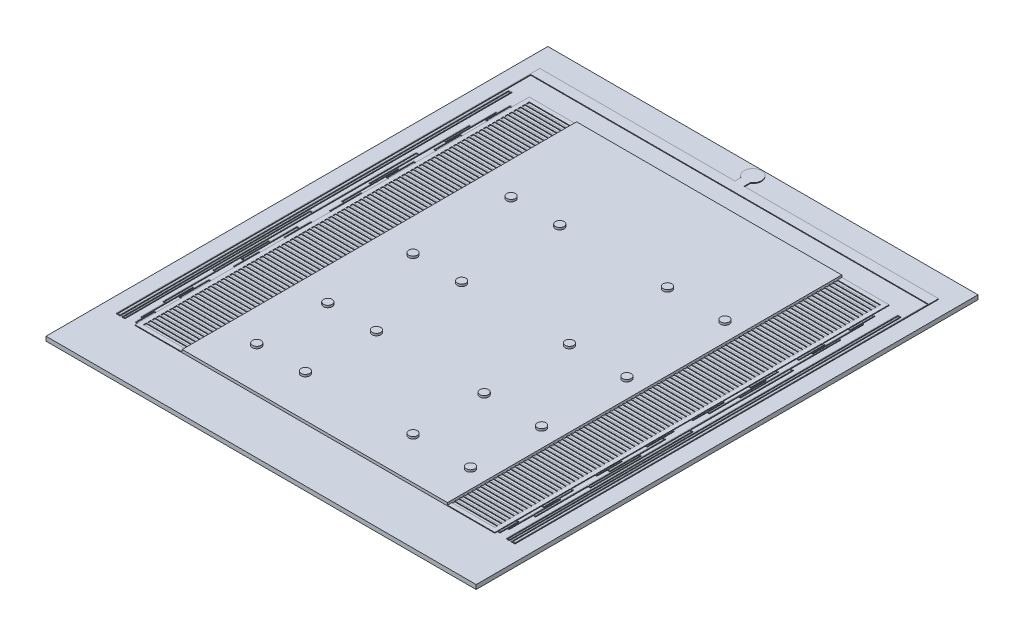
SolidWorks part; units mm, degrees
ref_plane "Front Plane" through (0, 0, 0) normal (0, 0, 1) x (1, 0, 0)
ref_plane "Top Plane" through (0, 0, 0) normal (0, 1, 0) x (1, 0, 0)
ref_plane "Right Plane" through (0, 0, 0) normal (1, 0, 0) x (0, 0, -1)
sketch "Sketch3" plane through (0, 0, 0) normal (0, 1, 0) x (1, 0, 0)
  line L1 (-15, 17.5) -> (15, 17.5)
  line L2 (-15, 17.5) -> (-15, -17.5)
  line L3 (-15, -17.5) -> (15, -17.5)
  line L4 (15, 17.5) -> (15, -17.5)
  line L5 (-15, 17.5) -> (15, -17.5) construction
  line L6 (-15, -17.5) -> (15, 17.5) construction
  point P0 (0, 0)
  dimension "D1" = 30
  dimension "D2" = 35
extrude "Boss-Extrude2" add sketch "Sketch3" along normal blind 0.3
sketch "Sketch4" plane through (0, 0.3, 0) normal (0, 1, 0) x (1, 0, 0)
  line L1 (-9.25, 13.75) -> (9.25, 13.75)
  line L2 (-9.25, 13.75) -> (-9.25, -13.75)
  line L3 (-9.25, -13.75) -> (9.25, -13.75)
  line L4 (9.25, 13.75) -> (9.25, -13.75)
  line L5 (-9.25, 13.75) -> (9.25, -13.75) construction
  line L6 (-9.25, -13.75) -> (9.25, 13.75) construction
  point P0 (0, 0)
  dimension "D1" = 18.5
  dimension "D2" = 27.5
sketch "Sketch6" plane through (0, 0.3, 0) normal (0, 1, 0) x (1, 0, 0)
  line L0 (-13.905, 15.8474) -> (13.905, 15.8474)
  line L1 (13.905, 15.8474) -> (13.905, -13.6942)
  line L2 (-13.905, 15.8474) -> (-13.905, -13.6942)
  line L3 (-9.25, 13.75) -> (-9.25, -13.75)
  line L4 (-9.25, 13.75) -> (-12.55, 13.75)
  line L5 (-9.25, -13.75) -> (-12.55, -13.75)
  line L6 (-12.55, 13.75) -> (-12.55, -13.75)
  line L7 (9.25, 13.75) -> (9.25, -13.75)
  line L8 (9.25, 13.75) -> (12.55, 13.75)
  line L9 (9.25, -13.75) -> (12.55, -13.75)
  line L10 (12.55, 13.75) -> (12.55, -13.75)
  line L11 (-12.55, 12.5818) -> (-12.7178, 12.5818)
  line L12 (-12.55, 12.5318) -> (-12.6678, 12.5318)
  line L13 (-12.55, 10.928) -> (-12.6678, 10.928)
  line L14 (-12.55, 10.878) -> (-12.7178, 10.878)
  line L15 (-12.6678, 12.5318) -> (-12.6678, 10.928)
  line L16 (-12.7178, 12.5818) -> (-12.7178, 11.7021)
  line L17 (-12.7178, 11.7021) -> (-12.8193, 11.7021)
  line L18 (-12.7178, 10.878) -> (-12.7178, 11.6521)
  line L19 (-12.7178, 11.6521) -> (-12.7693, 11.6521)
  line L20 (-12.55, 9.1125) -> (-12.7178, 9.1125)
  line L21 (-12.55, 9.0625) -> (-12.6678, 9.0625)
  line L22 (-12.6678, 9.0625) -> (-12.6678, 7.3412)
  line L23 (-12.6678, 7.3412) -> (-12.55, 7.3412)
  line L24 (-12.55, 7.2912) -> (-12.7178, 7.2912)
  line L25 (-12.7178, 7.2912) -> (-12.7178, 8.1575)
  line L26 (-12.8193, 11.7021) -> (-12.8193, 9.9736)
  line L27 (-12.7178, 9.1125) -> (-12.7178, 8.2075)
  line L28 (-12.7178, 8.2075) -> (-12.7693, 8.2075)
  line L29 (-12.55, 5.8632) -> (-12.7178, 5.8632)
  line L30 (-12.7178, 5.8632) -> (-12.7178, 4.8722)
  line L31 (-12.7178, 4.8722) -> (-12.8274, 4.8722)
  line L32 (-12.55, 3.9456) -> (-12.7178, 3.9456)
  line L33 (-12.7178, 3.9456) -> (-12.7178, 4.8222)
  line L34 (-12.7178, 4.8222) -> (-12.7774, 4.8222)
  line L35 (-12.55, 5.8132) -> (-12.6678, 5.8132)
  line L36 (-12.6678, 5.8132) -> (-12.6678, 3.9956)
  line L37 (-12.6678, 3.9956) -> (-12.55, 3.9956)
  line L38 (-12.55, 2.1314) -> (-12.6674, 2.1314)
  line L39 (-12.6674, 2.1314) -> (-12.6674, 0.9895)
  line L40 (-12.6674, 0.9895) -> (-12.7774, 0.9895)
  line L41 (-12.55, -0.05) -> (-12.6674, -0.05)
  line L42 (-12.6674, -0.05) -> (-12.6674, 0.9395)
  line L43 (-12.8274, 4.8722) -> (-12.8274, 3.0344)
  line L44 (-12.55, 2.0814) -> (-12.6174, 2.0814)
  line L45 (-12.6174, 2.0814) -> (-12.6174, 0)
  line L46 (-12.6174, 0) -> (-12.55, 0)
  line L47 (-12.55, -1.363) -> (-12.6674, -1.363)
  line L48 (-12.6674, -1.363) -> (-12.6674, -2.1377)
  line L49 (-12.8274, 3.0344) -> (-12.9034, 3.0344)
  line L50 (-12.55, -3.2374) -> (-12.6674, -3.2374)
  line L51 (-12.6674, -3.2374) -> (-12.6674, -2.1877)
  line L52 (-12.6674, -2.1877) -> (-12.8051, -2.1877)
  line L53 (-12.55, -1.413) -> (-12.6174, -1.413)
  line L54 (-12.6174, -1.413) -> (-12.6174, -3.1874)
  line L55 (-12.6174, -3.1874) -> (-12.55, -3.1874)
  line L56 (-12.55, -4.9884) -> (-12.6674, -4.9884)
  line L57 (-12.6674, -4.9884) -> (-12.6674, -5.9807)
  line L58 (-12.6674, -5.9807) -> (-12.8051, -5.9807)
  line L59 (-12.55, -6.7484) -> (-12.6674, -6.7484)
  line L60 (-12.6674, -6.7484) -> (-12.6674, -6.0307)
  line L61 (-12.6674, 0.9395) -> (-12.8274, 0.9395)
  line L62 (-12.6174, -5.0384) -> (-12.6174, -6.6984)
  line L63 (-12.6174, -6.6984) -> (-12.55, -6.6984)
  line L64 (-12.6174, -5.0384) -> (-12.55, -5.0384)
  line L65 (-12.55, -8.422) -> (-12.7178, -8.422)
  line L66 (-12.7178, -8.422) -> (-12.7178, -9.4377)
  line L67 (-12.8274, 0.9395) -> (-12.8274, 2.9844)
  line L68 (-12.55, -10.502) -> (-12.7178, -10.502)
  line L69 (-12.7178, -10.502) -> (-12.7178, -9.4877)
  line L70 (-12.7178, -9.4877) -> (-12.7793, -9.4877)
  line L71 (-12.55, -8.472) -> (-12.6678, -8.472)
  line L72 (-12.6678, -8.472) -> (-12.6678, -10.452)
  line L73 (-12.6678, -10.452) -> (-12.55, -10.452)
  line L74 (-12.55, -12.2327) -> (-12.7178, -12.2327)
  line L75 (-12.7178, -12.2327) -> (-12.7178, -12.9898)
  line L76 (-12.7178, -12.9898) -> (-12.7793, -12.9898)
  line L77 (-12.55, -13.5571) -> (-12.7178, -13.5571)
  line L78 (-12.7178, -13.5571) -> (-12.7178, -13.0398)
  line L79 (-12.8193, 9.9736) -> (-12.9534, 9.9736)
  line L80 (-12.6678, -12.2827) -> (-12.6678, -13.5071)
  line L81 (-12.6678, -13.5071) -> (-12.55, -13.5071)
  line L82 (-12.9534, 9.9736) -> (-12.9534, 6.4717)
  line L83 (-12.7178, 8.1575) -> (-12.8193, 8.1575)
  line L84 (-12.8193, 8.1575) -> (-12.8193, 9.9236)
  line L85 (-12.8193, 9.9236) -> (-12.9034, 9.9236)
  line L86 (-12.7693, 11.6521) -> (-12.7693, 8.2075)
  line L87 (-12.7774, 4.8222) -> (-12.7774, 0.9895)
  line L88 (-12.6674, -6.0307) -> (-12.8551, -6.0307)
  line L89 (-12.8551, -6.0307) -> (-12.8551, -4.0382)
  line L90 (-12.8551, -4.0382) -> (-12.9467, -4.0382)
  line L91 (-12.6674, -2.1377) -> (-12.8551, -2.1377)
  line L92 (-12.8551, -2.1377) -> (-12.8551, -3.9882)
  line L93 (-12.8551, -3.9882) -> (-12.9967, -3.9882)
  line L94 (-12.8051, -2.1877) -> (-12.8051, -5.9807)
  line L95 (-12.7178, -9.4377) -> (-12.8293, -9.4377)
  line L96 (-12.8293, -9.4377) -> (-12.8293, -11.3027)
  line L97 (-12.8293, -11.3027) -> (-12.9467, -11.3027)
  line L98 (-12.7178, -13.0398) -> (-12.8293, -13.0398)
  line L99 (-12.8293, -13.0398) -> (-12.8293, -11.3527)
  line L100 (-12.9967, -3.9882) -> (-12.9967, -7.6362)
  line L101 (-12.7793, -9.4877) -> (-12.7793, -12.9898)
  line L102 (-12.9534, 6.4717) -> (-13.1543, 6.4717)
  line L103 (-12.9534, 2.9844) -> (-12.9534, 6.4217)
  line L104 (-12.9534, 6.4217) -> (-13.1043, 6.4217)
  line L105 (-12.9034, 9.9236) -> (-12.9034, 3.0344)
  line L106 (-12.9534, 2.9844) -> (-12.8274, 2.9844)
  line L107 (-12.9967, -7.6362) -> (-13.1043, -7.6362)
  line L108 (-12.8293, -11.3527) -> (-12.9967, -11.3527)
  line L109 (-12.9967, -11.3527) -> (-12.9967, -7.6862)
  line L110 (-13.1543, 6.4717) -> (-13.1543, -0.7267)
  line L111 (-12.9467, -4.0382) -> (-12.9467, -11.3027)
  line L112 (-13.1543, -0.7267) -> (-13.3496, -0.7267)
  line L113 (-12.9967, -7.6862) -> (-13.1543, -7.6862)
  line L114 (-13.1543, -7.6862) -> (-13.1543, -0.7767)
  line L115 (-13.1043, -7.6362) -> (-13.1043, 6.4217)
  line L116 (-12.6678, -12.2827) -> (-12.55, -12.2827)
  line L117 (-13.905, -13.6942) -> (-13.6359, -13.6942)
  line L118 (-13.855, 15.1627) -> (13.855, 15.1627)
  line L119 (-13.855, 15.1627) -> (-13.855, -13.6442)
  line L120 (-13.855, -13.6442) -> (-13.6859, -13.6442)
  line L121 (-13.6859, -13.6442) -> (-13.6859, 13.4436)
  line L122 (-13.6859, 13.4436) -> (-13.461, 13.4436)
  line L123 (-13.461, 13.4436) -> (-13.461, -13.646)
  line L124 (-13.461, -13.646) -> (-13.3496, -13.646)
  line L125 (-13.3496, -13.646) -> (-13.3496, -0.7267)
  line L126 (-13.6359, -13.6942) -> (-13.6359, 13.3936)
  line L127 (-13.6359, 13.3936) -> (-13.511, 13.3936)
  line L128 (-13.511, 13.3936) -> (-13.511, -13.696)
  line L129 (-13.511, -13.696) -> (-13.2996, -13.696)
  line L130 (-13.2996, -13.696) -> (-13.2996, -0.7767)
  line L131 (-13.2996, -0.7767) -> (-13.1543, -0.7767)
  line L132 (0, -18.8163) -> (0, 18.8163) construction
  line L134 (13.855, 15.1627) -> (13.855, -13.6442)
  line L135 (13.511, -13.696) -> (13.2996, -13.696)
  line L136 (13.461, -13.646) -> (13.3496, -13.646)
  line L137 (13.905, -13.6942) -> (13.6359, -13.6942)
  line L138 (13.855, -13.6442) -> (13.6859, -13.6442)
  line L139 (12.7178, -13.5571) -> (12.7178, -13.0398)
  line L140 (12.55, -13.5571) -> (12.7178, -13.5571)
  line L141 (12.6678, -13.5071) -> (12.55, -13.5071)
  line L142 (12.7178, -13.0398) -> (12.8293, -13.0398)
  line L143 (12.7178, -12.9898) -> (12.7793, -12.9898)
  line L144 (12.6678, -12.2827) -> (12.55, -12.2827)
  line L145 (12.7178, -12.2327) -> (12.7178, -12.9898)
  line L146 (12.6678, -12.2827) -> (12.6678, -13.5071)
  line L147 (12.55, -12.2327) -> (12.7178, -12.2327)
  line L148 (12.8293, -13.0398) -> (12.8293, -11.3527)
  line L149 (12.8293, -11.3527) -> (12.9967, -11.3527)
  line L150 (12.8293, -11.3027) -> (12.9467, -11.3027)
  line L151 (12.55, -10.502) -> (12.7178, -10.502)
  line L152 (12.6678, -10.452) -> (12.55, -10.452)
  line L153 (12.7178, -10.502) -> (12.7178, -9.4877)
  line L154 (12.8293, -9.4377) -> (12.8293, -11.3027)
  line L155 (12.7793, -9.4877) -> (12.7793, -12.9898)
  line L156 (12.7178, -9.4877) -> (12.7793, -9.4877)
  line L157 (12.7178, -9.4377) -> (12.8293, -9.4377)
  line L158 (12.7178, -8.422) -> (12.7178, -9.4377)
  line L159 (12.6678, -8.472) -> (12.6678, -10.452)
  line L160 (12.55, -8.472) -> (12.6678, -8.472)
  line L161 (12.55, -8.422) -> (12.7178, -8.422)
  line L162 (12.9967, -11.3527) -> (12.9967, -7.6862)
  line L163 (12.9967, -7.6862) -> (13.1543, -7.6862)
  line L164 (12.9967, -7.6362) -> (13.1043, -7.6362)
  line L165 (12.55, -6.7484) -> (12.6674, -6.7484)
  line L166 (12.6174, -6.6984) -> (12.55, -6.6984)
  line L167 (12.6674, -6.7484) -> (12.6674, -6.0307)
  line L168 (12.6674, -6.0307) -> (12.8551, -6.0307)
  line L169 (12.6674, -5.9807) -> (12.8051, -5.9807)
  line L170 (12.6674, -4.9884) -> (12.6674, -5.9807)
  line L171 (12.6174, -5.0384) -> (12.6174, -6.6984)
  line L172 (12.6174, -5.0384) -> (12.55, -5.0384)
  line L173 (12.55, -4.9884) -> (12.6674, -4.9884)
  line L174 (12.8551, -6.0307) -> (12.8551, -4.0382)
  line L175 (12.9967, -3.9882) -> (12.9967, -7.6362)
  line L176 (12.9467, -4.0382) -> (12.9467, -11.3027)
  line L177 (12.8551, -4.0382) -> (12.9467, -4.0382)
  line L178 (12.8551, -3.9882) -> (12.9967, -3.9882)
  line L179 (12.55, -3.2374) -> (12.6674, -3.2374)
  line L180 (12.6174, -3.1874) -> (12.55, -3.1874)
  line L181 (12.8551, -2.1377) -> (12.8551, -3.9882)
  line L182 (12.8051, -2.1877) -> (12.8051, -5.9807)
  line L183 (12.6674, -3.2374) -> (12.6674, -2.1877)
  line L184 (12.6674, -2.1877) -> (12.8051, -2.1877)
  line L185 (12.6674, -2.1377) -> (12.8551, -2.1377)
  line L186 (12.6174, -1.413) -> (12.6174, -3.1874)
  line L187 (12.6674, -1.363) -> (12.6674, -2.1377)
  line L188 (12.55, -1.413) -> (12.6174, -1.413)
  line L189 (12.55, -1.363) -> (12.6674, -1.363)
  line L190 (13.1543, -7.6862) -> (13.1543, -0.7767)
  line L191 (13.2996, -13.696) -> (13.2996, -0.7767)
  line L192 (13.3496, -13.646) -> (13.3496, -0.7267)
  line L193 (13.2996, -0.7767) -> (13.1543, -0.7767)
  line L194 (13.1543, -0.7267) -> (13.3496, -0.7267)
  line L195 (12.55, -0.05) -> (12.6674, -0.05)
  line L196 (12.6174, 0) -> (12.55, 0)
  line L197 (12.6674, -0.05) -> (12.6674, 0.9395)
  line L198 (12.6674, 0.9395) -> (12.8274, 0.9395)
  line L199 (12.6674, 0.9895) -> (12.7774, 0.9895)
  line L200 (12.6174, 2.0814) -> (12.6174, 0)
  line L201 (12.6674, 2.1314) -> (12.6674, 0.9895)
  line L202 (12.55, 2.0814) -> (12.6174, 2.0814)
  line L203 (12.55, 2.1314) -> (12.6674, 2.1314)
  line L204 (12.8274, 3.0344) -> (12.9034, 3.0344)
  line L205 (12.9534, 2.9844) -> (12.8274, 2.9844)
  line L206 (12.8274, 0.9395) -> (12.8274, 2.9844)
  line L207 (12.55, 3.9456) -> (12.7178, 3.9456)
  line L208 (12.6678, 3.9956) -> (12.55, 3.9956)
  line L209 (12.8274, 4.8722) -> (12.8274, 3.0344)
  line L210 (12.7774, 4.8222) -> (12.7774, 0.9895)
  line L211 (12.7178, 3.9456) -> (12.7178, 4.8222)
  line L212 (12.7178, 4.8222) -> (12.7774, 4.8222)
  line L213 (12.7178, 4.8722) -> (12.8274, 4.8722)
  line L214 (12.6678, 5.8132) -> (12.6678, 3.9956)
  line L215 (12.7178, 5.8632) -> (12.7178, 4.8722)
  line L216 (12.55, 5.8132) -> (12.6678, 5.8132)
  line L217 (12.55, 5.8632) -> (12.7178, 5.8632)
  line L218 (12.9534, 2.9844) -> (12.9534, 6.4217)
  line L219 (13.1543, 6.4717) -> (13.1543, -0.7267)
  line L220 (13.1043, -7.6362) -> (13.1043, 6.4217)
  line L221 (12.9534, 6.4217) -> (13.1043, 6.4217)
  line L222 (12.9534, 6.4717) -> (13.1543, 6.4717)
  line L223 (12.55, 7.2912) -> (12.7178, 7.2912)
  line L224 (12.6678, 7.3412) -> (12.55, 7.3412)
  line L225 (12.7178, 7.2912) -> (12.7178, 8.1575)
  line L226 (12.7178, 8.1575) -> (12.8193, 8.1575)
  line L227 (12.7178, 8.2075) -> (12.7693, 8.2075)
  line L228 (12.6678, 9.0625) -> (12.6678, 7.3412)
  line L229 (12.7178, 9.1125) -> (12.7178, 8.2075)
  line L230 (12.55, 9.0625) -> (12.6678, 9.0625)
  line L231 (12.55, 9.1125) -> (12.7178, 9.1125)
  line L232 (12.8193, 8.1575) -> (12.8193, 9.9236)
  line L233 (12.9534, 9.9736) -> (12.9534, 6.4717)
  line L234 (12.9034, 9.9236) -> (12.9034, 3.0344)
  line L235 (12.8193, 9.9236) -> (12.9034, 9.9236)
  line L236 (12.8193, 9.9736) -> (12.9534, 9.9736)
  line L237 (12.55, 10.878) -> (12.7178, 10.878)
  line L238 (12.55, 10.928) -> (12.6678, 10.928)
  line L239 (12.8193, 11.7021) -> (12.8193, 9.9736)
  line L240 (12.7693, 11.6521) -> (12.7693, 8.2075)
  line L241 (12.7178, 10.878) -> (12.7178, 11.6521)
  line L242 (12.7178, 11.6521) -> (12.7693, 11.6521)
  line L243 (12.7178, 11.7021) -> (12.8193, 11.7021)
  line L244 (13.461, 13.4436) -> (13.461, -13.646)
  line L245 (13.511, 13.3936) -> (13.511, -13.696)
  line L246 (13.6359, -13.6942) -> (13.6359, 13.3936)
  line L247 (13.6859, -13.6442) -> (13.6859, 13.4436)
  line L248 (13.6359, 13.3936) -> (13.511, 13.3936)
  line L249 (13.6859, 13.4436) -> (13.461, 13.4436)
  line L250 (12.6678, 12.5318) -> (12.6678, 10.928)
  line L251 (12.7178, 12.5818) -> (12.7178, 11.7021)
  line L252 (12.55, 12.5318) -> (12.6678, 12.5318)
  line L253 (12.55, 12.5818) -> (12.7178, 12.5818)
  line L254 (-0.2968, 16.2659) -> (-0.2968, 15.8474)
  line L255 (0.336, 16.2899) -> (0.336, 15.8474)
  circle A0 centre (0, 16.7949) radius 0.6065
  point P0 (-12.55, 0)
  point P3 (0, 15.8474)
  point P14 (-12.55, 0)
  point P19 (-12.55, 7.2912)
  point P21 (-12.55, 10.928)
  point P22 (-12.55, 12.4686)
  point P23 (-12.55, 9.0625)
  point P24 (-12.55, 3.9833)
  point P25 (-12.55, 5.8132)
  point P26 (-12.55, 2.0814)
  point P27 (-12.55, -6.7484)
  point P28 (-12.55, -3.2374)
  point P29 (-12.55, -1.413)
  point P30 (-12.55, -5.0384)
  point P31 (-12.55, -10.502)
  point P32 (-12.55, -8.472)
  point P33 (-12.55, -12.1448)
  point P157 (-13.227, -0.7767)
  point P158 (-12.5837, -6.6984)
  point P162 (0, 15.1627)
  point P177 (0, 0)
  dimension "D1" = 3.3
  dimension "D2" = 3.3
  dimension "D3" = 27.81
  dimension "D4" = 0.05
  dimension "D5" = 0.05
  dimension "D6" = 0.05
  dimension "D7" = 0.05
  dimension "D8" = 0.05
  dimension "D9" = 0.05
  dimension "D10" = 0.05
  dimension "D11" = 0.05
  dimension "D12" = 0.05
  dimension "D13" = 0.05
  dimension "D14" = 0.05
  dimension "D15" = 0.05
  dimension "D16" = 0.05
  dimension "D17" = 0.05
  dimension "D18" = 0.05
  dimension "D19" = 0.05
  dimension "D20" = 0.05
  dimension "D21" = 0.05
  dimension "D22" = 0.05
  dimension "D23" = 0.05
  dimension "D24" = 0.05
  dimension "D25" = 0.05
  dimension "D26" = 0.05
  dimension "D27" = 0.05
  dimension "D28" = 0.05
  dimension "D29" = 0.05
  dimension "D30" = 0.05
  dimension "D31" = 0.05
  dimension "D32" = 0.05
  dimension "D33" = 0.05
  dimension "D34" = 0.05
  dimension "D35" = 0.05
  dimension "D36" = 0.05
  dimension "D37" = 0.05
  dimension "D38" = 0.05
  dimension "D39" = 0.05
  dimension "D40" = 0.05
  dimension "D41" = 0.05
  dimension "D42" = 0.05
  dimension "D43" = 0.05
  dimension "D44" = 0.05
  dimension "D45" = 0.05
  dimension "D46" = 0.05
  dimension "D47" = 0.05
  dimension "D48" = 0.05
  dimension "D49" = 0.05
  dimension "D50" = 0.05
  dimension "D51" = 0.05
  dimension "D52" = 0.05
  dimension "D53" = 0.05
  dimension "D54" = 0.05
  dimension "D55" = 0.05
  dimension "D56" = 0.05
extrude "Boss-Extrude5" add sketch "Sketch4" along normal blind 0.2 separate body
extrude "Boss-Extrude10" add sketch "Sketch6" along normal blind 0.05 contours L132 L118 L134 L138 L247 L249 L244 L136 L192 L194 L219 L222 L233 L236 L239 L243 L251 L253 L10 L252 L250 L238 L237 L241 L242 L240 L227 L229 L231 L230 L228 L224 L223 L225 L226 L232 L235 L234 L204 L209 L213 L215 L217 L216 L214 L208 | L0 L132 A0 L254 | L132 L0 L255 A0 | A0 L132 | L132 A0 | L118 L132 L0 L2 L117 L126 L127 L128 L129 L130 L131 L114 L113 L109 L108 L99 L98 L78 L77 L6 L81 L80 L116 L74 L75 L76 L101 L70 L69 L68 L73 L72 L71 L65 L66 L95 L96 L97 L111 L90 L89 L88 L60 L59 L63 L62 | L10 L8 L7 L9 | L4 L6 L5 L3 | L3 L4 L6 L5 | L7 L8 L10 L9 region at (-7.1009, 0.3, -15.5209) region at (-0.1536, 0.3, -16.0312) region at (0.1754, 0.3, -16.0354) region at (0.168, 0.3, -15.5209) region at (-0.2574, 0.3, -16.7949) region at (0.2574, 0.3, -16.7949) region at (-10.9, 0.3, 0) region at (10.9, 0.3, 0)
sketch "Sketch7" plane through (0, 0.3, 0) normal (0, 1, 0) x (1, 0, 0)
  line L0 (9.25, 13.45) -> (12.25, 13.45)
  line L1 (9.25, 13.45) -> (9.25, 13.25)
  line L2 (12.25, 13.45) -> (12.25, 13.25)
  line L3 (9.25, 13.25) -> (12.25, 13.25)
  line L4 (9.25, -13.75) -> (9.25, 13.75) construction
  line L7 (9.25, 13.15) -> (12.25, 13.15)
  line L8 (9.25, 13.15) -> (9.25, 12.95)
  line L9 (9.25, 12.95) -> (12.25, 12.95)
  line L10 (12.25, 13.15) -> (12.25, 12.95)
  line L11 (9.25, 12.85) -> (12.25, 12.85)
  line L12 (9.25, 12.85) -> (9.25, 12.65)
  line L13 (9.25, 12.65) -> (12.25, 12.65)
  line L14 (12.25, 12.85) -> (12.25, 12.65)
  line L15 (9.25, 12.55) -> (12.25, 12.55)
  line L16 (9.25, 12.55) -> (9.25, 12.35)
  line L17 (9.25, 12.35) -> (12.25, 12.35)
  line L18 (12.25, 12.55) -> (12.25, 12.35)
  line L19 (9.25, 12.25) -> (12.25, 12.25)
  line L20 (9.25, 12.25) -> (9.25, 12.05)
  line L21 (9.25, 12.05) -> (12.25, 12.05)
  line L22 (12.25, 12.25) -> (12.25, 12.05)
  line L23 (9.25, 11.95) -> (12.25, 11.95)
  line L24 (9.25, 11.95) -> (9.25, 11.75)
  line L25 (9.25, 11.75) -> (12.25, 11.75)
  line L26 (12.25, 11.95) -> (12.25, 11.75)
  line L27 (9.25, 11.65) -> (12.25, 11.65)
  line L28 (9.25, 11.65) -> (9.25, 11.45)
  line L29 (9.25, 11.45) -> (12.25, 11.45)
  line L30 (12.25, 11.65) -> (12.25, 11.45)
  line L31 (9.25, 11.35) -> (12.25, 11.35)
  line L32 (9.25, 11.35) -> (9.25, 11.15)
  line L33 (9.25, 11.15) -> (12.25, 11.15)
  line L34 (12.25, 11.35) -> (12.25, 11.15)
  line L35 (9.25, 11.05) -> (12.25, 11.05)
  line L36 (9.25, 11.05) -> (9.25, 10.85)
  line L37 (9.25, 10.85) -> (12.25, 10.85)
  line L38 (12.25, 11.05) -> (12.25, 10.85)
  line L39 (9.25, 10.75) -> (12.25, 10.75)
  line L40 (9.25, 10.75) -> (9.25, 10.55)
  line L41 (9.25, 10.55) -> (12.25, 10.55)
  line L42 (12.25, 10.75) -> (12.25, 10.55)
  line L43 (9.25, 10.45) -> (12.25, 10.45)
  line L44 (9.25, 10.45) -> (9.25, 10.25)
  line L45 (9.25, 10.25) -> (12.25, 10.25)
  line L46 (12.25, 10.45) -> (12.25, 10.25)
  line L47 (9.25, 10.15) -> (12.25, 10.15)
  line L48 (9.25, 10.15) -> (9.25, 9.95)
  line L49 (9.25, 9.95) -> (12.25, 9.95)
  line L50 (12.25, 10.15) -> (12.25, 9.95)
  line L51 (9.25, 9.85) -> (12.25, 9.85)
  line L52 (9.25, 9.85) -> (9.25, 9.65)
  line L53 (9.25, 9.65) -> (12.25, 9.65)
  line L54 (12.25, 9.85) -> (12.25, 9.65)
  line L55 (9.25, 9.55) -> (12.25, 9.55)
  line L56 (9.25, 9.55) -> (9.25, 9.35)
  line L57 (9.25, 9.35) -> (12.25, 9.35)
  line L58 (12.25, 9.55) -> (12.25, 9.35)
  line L59 (9.25, 9.25) -> (12.25, 9.25)
  line L60 (9.25, 9.25) -> (9.25, 9.05)
  line L61 (9.25, 9.05) -> (12.25, 9.05)
  line L62 (12.25, 9.25) -> (12.25, 9.05)
  line L63 (9.25, 8.95) -> (12.25, 8.95)
  line L64 (9.25, 8.95) -> (9.25, 8.75)
  line L65 (9.25, 8.75) -> (12.25, 8.75)
  line L66 (12.25, 8.95) -> (12.25, 8.75)
  line L67 (9.25, 8.65) -> (12.25, 8.65)
  line L68 (9.25, 8.65) -> (9.25, 8.45)
  line L69 (9.25, 8.45) -> (12.25, 8.45)
  line L70 (12.25, 8.65) -> (12.25, 8.45)
  line L71 (9.25, 8.35) -> (12.25, 8.35)
  line L72 (9.25, 8.35) -> (9.25, 8.15)
  line L73 (9.25, 8.15) -> (12.25, 8.15)
  line L74 (12.25, 8.35) -> (12.25, 8.15)
  line L75 (9.25, 8.05) -> (12.25, 8.05)
  line L76 (9.25, 8.05) -> (9.25, 7.85)
  line L77 (9.25, 7.85) -> (12.25, 7.85)
  line L78 (12.25, 8.05) -> (12.25, 7.85)
  line L79 (9.25, 7.75) -> (12.25, 7.75)
  line L80 (9.25, 7.75) -> (9.25, 7.55)
  line L81 (9.25, 7.55) -> (12.25, 7.55)
  line L82 (12.25, 7.75) -> (12.25, 7.55)
  line L83 (9.25, 7.45) -> (12.25, 7.45)
  line L84 (9.25, 7.45) -> (9.25, 7.25)
  line L85 (9.25, 7.25) -> (12.25, 7.25)
  line L86 (12.25, 7.45) -> (12.25, 7.25)
  line L87 (9.25, 7.15) -> (12.25, 7.15)
  line L88 (9.25, 7.15) -> (9.25, 6.95)
  line L89 (9.25, 6.95) -> (12.25, 6.95)
  line L90 (12.25, 7.15) -> (12.25, 6.95)
  line L91 (9.25, 6.85) -> (12.25, 6.85)
  line L92 (9.25, 6.85) -> (9.25, 6.65)
  line L93 (9.25, 6.65) -> (12.25, 6.65)
  line L94 (12.25, 6.85) -> (12.25, 6.65)
  line L95 (9.25, 6.55) -> (12.25, 6.55)
  line L96 (9.25, 6.55) -> (9.25, 6.35)
  line L97 (9.25, 6.35) -> (12.25, 6.35)
  line L98 (12.25, 6.55) -> (12.25, 6.35)
  line L99 (9.25, 6.25) -> (12.25, 6.25)
  line L100 (9.25, 6.25) -> (9.25, 6.05)
  line L101 (9.25, 6.05) -> (12.25, 6.05)
  line L102 (12.25, 6.25) -> (12.25, 6.05)
  line L103 (9.25, 5.95) -> (12.25, 5.95)
  line L104 (9.25, 5.95) -> (9.25, 5.75)
  line L105 (9.25, 5.75) -> (12.25, 5.75)
  line L106 (12.25, 5.95) -> (12.25, 5.75)
  line L107 (9.25, 5.65) -> (12.25, 5.65)
  line L108 (9.25, 5.65) -> (9.25, 5.45)
  line L109 (9.25, 5.45) -> (12.25, 5.45)
  line L110 (12.25, 5.65) -> (12.25, 5.45)
  line L111 (9.25, 5.35) -> (12.25, 5.35)
  line L112 (9.25, 5.35) -> (9.25, 5.15)
  line L113 (9.25, 5.15) -> (12.25, 5.15)
  line L114 (12.25, 5.35) -> (12.25, 5.15)
  line L115 (9.25, 5.05) -> (12.25, 5.05)
  line L116 (9.25, 5.05) -> (9.25, 4.85)
  line L117 (9.25, 4.85) -> (12.25, 4.85)
  line L118 (12.25, 5.05) -> (12.25, 4.85)
  line L119 (9.25, 4.75) -> (12.25, 4.75)
  line L120 (9.25, 4.75) -> (9.25, 4.55)
  line L121 (9.25, 4.55) -> (12.25, 4.55)
  line L122 (12.25, 4.75) -> (12.25, 4.55)
  line L123 (9.25, 4.45) -> (12.25, 4.45)
  line L124 (9.25, 4.45) -> (9.25, 4.25)
  line L125 (9.25, 4.25) -> (12.25, 4.25)
  line L126 (12.25, 4.45) -> (12.25, 4.25)
  line L127 (9.25, 4.15) -> (12.25, 4.15)
  line L128 (9.25, 4.15) -> (9.25, 3.95)
  line L129 (9.25, 3.95) -> (12.25, 3.95)
  line L130 (12.25, 4.15) -> (12.25, 3.95)
  line L131 (9.25, 3.85) -> (12.25, 3.85)
  line L132 (9.25, 3.85) -> (9.25, 3.65)
  line L133 (9.25, 3.65) -> (12.25, 3.65)
  line L134 (12.25, 3.85) -> (12.25, 3.65)
  line L135 (9.25, 3.55) -> (12.25, 3.55)
  line L136 (9.25, 3.55) -> (9.25, 3.35)
  line L137 (9.25, 3.35) -> (12.25, 3.35)
  line L138 (12.25, 3.55) -> (12.25, 3.35)
  line L139 (9.25, 3.25) -> (12.25, 3.25)
  line L140 (9.25, 3.25) -> (9.25, 3.05)
  line L141 (9.25, 3.05) -> (12.25, 3.05)
  line L142 (12.25, 3.25) -> (12.25, 3.05)
  line L143 (9.25, 2.95) -> (12.25, 2.95)
  line L144 (9.25, 2.95) -> (9.25, 2.75)
  line L145 (9.25, 2.75) -> (12.25, 2.75)
  line L146 (12.25, 2.95) -> (12.25, 2.75)
  line L147 (9.25, 2.65) -> (12.25, 2.65)
  line L148 (9.25, 2.65) -> (9.25, 2.45)
  line L149 (9.25, 2.45) -> (12.25, 2.45)
  line L150 (12.25, 2.65) -> (12.25, 2.45)
  line L151 (9.25, 2.35) -> (12.25, 2.35)
  line L152 (9.25, 2.35) -> (9.25, 2.15)
  line L153 (9.25, 2.15) -> (12.25, 2.15)
  line L154 (12.25, 2.35) -> (12.25, 2.15)
  line L155 (9.25, 2.05) -> (12.25, 2.05)
  line L156 (9.25, 2.05) -> (9.25, 1.85)
  line L157 (9.25, 1.85) -> (12.25, 1.85)
  line L158 (12.25, 2.05) -> (12.25, 1.85)
  line L159 (9.25, 1.75) -> (12.25, 1.75)
  line L160 (9.25, 1.75) -> (9.25, 1.55)
  line L161 (9.25, 1.55) -> (12.25, 1.55)
  line L162 (12.25, 1.75) -> (12.25, 1.55)
  line L163 (9.25, 1.45) -> (12.25, 1.45)
  line L164 (9.25, 1.45) -> (9.25, 1.25)
  line L165 (9.25, 1.25) -> (12.25, 1.25)
  line L166 (12.25, 1.45) -> (12.25, 1.25)
  line L167 (9.25, 1.15) -> (12.25, 1.15)
  line L168 (9.25, 1.15) -> (9.25, 0.95)
  line L169 (9.25, 0.95) -> (12.25, 0.95)
  line L170 (12.25, 1.15) -> (12.25, 0.95)
  line L171 (9.25, 0.85) -> (12.25, 0.85)
  line L172 (9.25, 0.85) -> (9.25, 0.65)
  line L173 (9.25, 0.65) -> (12.25, 0.65)
  line L174 (12.25, 0.85) -> (12.25, 0.65)
  line L175 (9.25, 0.55) -> (12.25, 0.55)
  line L176 (9.25, 0.55) -> (9.25, 0.35)
  line L177 (9.25, 0.35) -> (12.25, 0.35)
  line L178 (12.25, 0.55) -> (12.25, 0.35)
  line L179 (9.25, 0.25) -> (12.25, 0.25)
  line L180 (9.25, 0.25) -> (9.25, 0.05)
  line L181 (9.25, 0.05) -> (12.25, 0.05)
  line L182 (12.25, 0.25) -> (12.25, 0.05)
  line L183 (9.25, -0.05) -> (12.25, -0.05)
  line L184 (9.25, -0.05) -> (9.25, -0.25)
  line L185 (9.25, -0.25) -> (12.25, -0.25)
  line L186 (12.25, -0.05) -> (12.25, -0.25)
  line L187 (9.25, -0.35) -> (12.25, -0.35)
  line L188 (9.25, -0.35) -> (9.25, -0.55)
  line L189 (9.25, -0.55) -> (12.25, -0.55)
  line L190 (12.25, -0.35) -> (12.25, -0.55)
  line L191 (9.25, -0.65) -> (12.25, -0.65)
  line L192 (9.25, -0.65) -> (9.25, -0.85)
  line L193 (9.25, -0.85) -> (12.25, -0.85)
  line L194 (12.25, -0.65) -> (12.25, -0.85)
  line L195 (9.25, -0.95) -> (12.25, -0.95)
  line L196 (9.25, -0.95) -> (9.25, -1.15)
  line L197 (9.25, -1.15) -> (12.25, -1.15)
  line L198 (12.25, -0.95) -> (12.25, -1.15)
  line L199 (9.25, -1.25) -> (12.25, -1.25)
  line L200 (9.25, -1.25) -> (9.25, -1.45)
  line L201 (9.25, -1.45) -> (12.25, -1.45)
  line L202 (12.25, -1.25) -> (12.25, -1.45)
  line L203 (9.25, -1.55) -> (12.25, -1.55)
  line L204 (9.25, -1.55) -> (9.25, -1.75)
  line L205 (9.25, -1.75) -> (12.25, -1.75)
  line L206 (12.25, -1.55) -> (12.25, -1.75)
  line L207 (9.25, -1.85) -> (12.25, -1.85)
  line L208 (9.25, -1.85) -> (9.25, -2.05)
  line L209 (9.25, -2.05) -> (12.25, -2.05)
  line L210 (12.25, -1.85) -> (12.25, -2.05)
  line L211 (9.25, -2.15) -> (12.25, -2.15)
  line L212 (9.25, -2.15) -> (9.25, -2.35)
  line L213 (9.25, -2.35) -> (12.25, -2.35)
  line L214 (12.25, -2.15) -> (12.25, -2.35)
  line L215 (9.25, -2.45) -> (12.25, -2.45)
  line L216 (9.25, -2.45) -> (9.25, -2.65)
  line L217 (9.25, -2.65) -> (12.25, -2.65)
  line L218 (12.25, -2.45) -> (12.25, -2.65)
  line L219 (9.25, -2.75) -> (12.25, -2.75)
  line L220 (9.25, -2.75) -> (9.25, -2.95)
  line L221 (9.25, -2.95) -> (12.25, -2.95)
  line L222 (12.25, -2.75) -> (12.25, -2.95)
  line L223 (9.25, -3.05) -> (12.25, -3.05)
  line L224 (9.25, -3.05) -> (9.25, -3.25)
  line L225 (9.25, -3.25) -> (12.25, -3.25)
  line L226 (12.25, -3.05) -> (12.25, -3.25)
  line L227 (9.25, -3.35) -> (12.25, -3.35)
  line L228 (9.25, -3.35) -> (9.25, -3.55)
  line L229 (9.25, -3.55) -> (12.25, -3.55)
  line L230 (12.25, -3.35) -> (12.25, -3.55)
  line L231 (9.25, -3.65) -> (12.25, -3.65)
  line L232 (9.25, -3.65) -> (9.25, -3.85)
  line L233 (9.25, -3.85) -> (12.25, -3.85)
  line L234 (12.25, -3.65) -> (12.25, -3.85)
  line L235 (9.25, -3.95) -> (12.25, -3.95)
  line L236 (9.25, -3.95) -> (9.25, -4.15)
  line L237 (9.25, -4.15) -> (12.25, -4.15)
  line L238 (12.25, -3.95) -> (12.25, -4.15)
  line L239 (9.25, -4.25) -> (12.25, -4.25)
  line L240 (9.25, -4.25) -> (9.25, -4.45)
  line L241 (9.25, -4.45) -> (12.25, -4.45)
  line L242 (12.25, -4.25) -> (12.25, -4.45)
  line L243 (9.25, -4.55) -> (12.25, -4.55)
  line L244 (9.25, -4.55) -> (9.25, -4.75)
  line L245 (9.25, -4.75) -> (12.25, -4.75)
  line L246 (12.25, -4.55) -> (12.25, -4.75)
  line L247 (9.25, -4.85) -> (12.25, -4.85)
  line L248 (9.25, -4.85) -> (9.25, -5.05)
  line L249 (9.25, -5.05) -> (12.25, -5.05)
  line L250 (12.25, -4.85) -> (12.25, -5.05)
  line L251 (9.25, -5.15) -> (12.25, -5.15)
  line L252 (9.25, -5.15) -> (9.25, -5.35)
  line L253 (9.25, -5.35) -> (12.25, -5.35)
  line L254 (12.25, -5.15) -> (12.25, -5.35)
  line L255 (9.25, -5.45) -> (12.25, -5.45)
  line L256 (9.25, -5.45) -> (9.25, -5.65)
  line L257 (9.25, -5.65) -> (12.25, -5.65)
  line L258 (12.25, -5.45) -> (12.25, -5.65)
  line L259 (9.25, -5.75) -> (12.25, -5.75)
  line L260 (9.25, -5.75) -> (9.25, -5.95)
  line L261 (9.25, -5.95) -> (12.25, -5.95)
  line L262 (12.25, -5.75) -> (12.25, -5.95)
  line L263 (9.25, -6.05) -> (12.25, -6.05)
  line L264 (9.25, -6.05) -> (9.25, -6.25)
  line L265 (9.25, -6.25) -> (12.25, -6.25)
  line L266 (12.25, -6.05) -> (12.25, -6.25)
  line L267 (9.25, -6.35) -> (12.25, -6.35)
  line L268 (9.25, -6.35) -> (9.25, -6.55)
  line L269 (9.25, -6.55) -> (12.25, -6.55)
  line L270 (12.25, -6.35) -> (12.25, -6.55)
  line L271 (9.25, -6.65) -> (12.25, -6.65)
  line L272 (9.25, -6.65) -> (9.25, -6.85)
  line L273 (9.25, -6.85) -> (12.25, -6.85)
  line L274 (12.25, -6.65) -> (12.25, -6.85)
  line L275 (9.25, -6.95) -> (12.25, -6.95)
  line L276 (9.25, -6.95) -> (9.25, -7.15)
  line L277 (9.25, -7.15) -> (12.25, -7.15)
  line L278 (12.25, -6.95) -> (12.25, -7.15)
  line L279 (9.25, -7.25) -> (12.25, -7.25)
  line L280 (9.25, -7.25) -> (9.25, -7.45)
  line L281 (9.25, -7.45) -> (12.25, -7.45)
  line L282 (12.25, -7.25) -> (12.25, -7.45)
  line L283 (9.25, -7.55) -> (12.25, -7.55)
  line L284 (9.25, -7.55) -> (9.25, -7.75)
  line L285 (9.25, -7.75) -> (12.25, -7.75)
  line L286 (12.25, -7.55) -> (12.25, -7.75)
  line L287 (9.25, -7.85) -> (12.25, -7.85)
  line L288 (9.25, -7.85) -> (9.25, -8.05)
  line L289 (9.25, -8.05) -> (12.25, -8.05)
  line L290 (12.25, -7.85) -> (12.25, -8.05)
  line L291 (9.25, -8.15) -> (12.25, -8.15)
  line L292 (9.25, -8.15) -> (9.25, -8.35)
  line L293 (9.25, -8.35) -> (12.25, -8.35)
  line L294 (12.25, -8.15) -> (12.25, -8.35)
  line L295 (9.25, -8.45) -> (12.25, -8.45)
  line L296 (9.25, -8.45) -> (9.25, -8.65)
  line L297 (9.25, -8.65) -> (12.25, -8.65)
  line L298 (12.25, -8.45) -> (12.25, -8.65)
  line L299 (9.25, -8.75) -> (12.25, -8.75)
  line L300 (9.25, -8.75) -> (9.25, -8.95)
  line L301 (9.25, -8.95) -> (12.25, -8.95)
  line L302 (12.25, -8.75) -> (12.25, -8.95)
  line L303 (9.25, -9.05) -> (12.25, -9.05)
  line L304 (9.25, -9.05) -> (9.25, -9.25)
  line L305 (9.25, -9.25) -> (12.25, -9.25)
  line L306 (12.25, -9.05) -> (12.25, -9.25)
  line L307 (9.25, -9.35) -> (12.25, -9.35)
  line L308 (9.25, -9.35) -> (9.25, -9.55)
  line L309 (9.25, -9.55) -> (12.25, -9.55)
  line L310 (12.25, -9.35) -> (12.25, -9.55)
  line L311 (9.25, -9.65) -> (12.25, -9.65)
  line L312 (9.25, -9.65) -> (9.25, -9.85)
  line L313 (9.25, -9.85) -> (12.25, -9.85)
  line L314 (12.25, -9.65) -> (12.25, -9.85)
  line L315 (9.25, -9.95) -> (12.25, -9.95)
  line L316 (9.25, -9.95) -> (9.25, -10.15)
  line L317 (9.25, -10.15) -> (12.25, -10.15)
  line L318 (12.25, -9.95) -> (12.25, -10.15)
  line L319 (9.25, -10.25) -> (12.25, -10.25)
  line L320 (9.25, -10.25) -> (9.25, -10.45)
  line L321 (9.25, -10.45) -> (12.25, -10.45)
  line L322 (12.25, -10.25) -> (12.25, -10.45)
  line L323 (9.25, -10.55) -> (12.25, -10.55)
  line L324 (9.25, -10.55) -> (9.25, -10.75)
  line L325 (9.25, -10.75) -> (12.25, -10.75)
  line L326 (12.25, -10.55) -> (12.25, -10.75)
  line L327 (9.25, -10.85) -> (12.25, -10.85)
  line L328 (9.25, -10.85) -> (9.25, -11.05)
  line L329 (9.25, -11.05) -> (12.25, -11.05)
  line L330 (12.25, -10.85) -> (12.25, -11.05)
  line L331 (9.25, -11.15) -> (12.25, -11.15)
  line L332 (9.25, -11.15) -> (9.25, -11.35)
  line L333 (9.25, -11.35) -> (12.25, -11.35)
  line L334 (12.25, -11.15) -> (12.25, -11.35)
  line L335 (9.25, -11.45) -> (12.25, -11.45)
  line L336 (9.25, -11.45) -> (9.25, -11.65)
  line L337 (9.25, -11.65) -> (12.25, -11.65)
  line L338 (12.25, -11.45) -> (12.25, -11.65)
  line L339 (9.25, -11.75) -> (12.25, -11.75)
  line L340 (9.25, -11.75) -> (9.25, -11.95)
  line L341 (9.25, -11.95) -> (12.25, -11.95)
  line L342 (12.25, -11.75) -> (12.25, -11.95)
  line L343 (9.25, -12.05) -> (12.25, -12.05)
  line L344 (9.25, -12.05) -> (9.25, -12.25)
  line L345 (9.25, -12.25) -> (12.25, -12.25)
  line L346 (12.25, -12.05) -> (12.25, -12.25)
  line L347 (9.25, -12.35) -> (12.25, -12.35)
  line L348 (9.25, -12.35) -> (9.25, -12.55)
  line L349 (9.25, -12.55) -> (12.25, -12.55)
  line L350 (12.25, -12.35) -> (12.25, -12.55)
  line L351 (9.25, -12.65) -> (12.25, -12.65)
  line L352 (9.25, -12.65) -> (9.25, -12.85)
  line L353 (9.25, -12.85) -> (12.25, -12.85)
  line L354 (12.25, -12.65) -> (12.25, -12.85)
  line L355 (9.25, -12.95) -> (12.25, -12.95)
  line L356 (9.25, -12.95) -> (9.25, -13.15)
  line L357 (9.25, -13.15) -> (12.25, -13.15)
  line L358 (12.25, -12.95) -> (12.25, -13.15)
  line L359 (9.25, -13.25) -> (12.25, -13.25)
  line L360 (9.25, -13.25) -> (9.25, -13.45)
  line L361 (9.25, -13.45) -> (12.25, -13.45)
  line L362 (12.25, -13.25) -> (12.25, -13.45)
  line L363 (-9.25, 13.45) -> (-9.25, 13.25)
  line L364 (-9.25, 13.45) -> (-12.25, 13.45)
  line L365 (-9.25, 13.25) -> (-12.25, 13.25)
  line L366 (-12.25, 13.45) -> (-12.25, 13.25)
  line L367 (-9.25, 13.75) -> (-9.25, -13.75) construction
  line L368 (-9.25, 13.15) -> (-9.25, 12.95)
  line L369 (-9.25, 13.15) -> (-12.25, 13.15)
  line L370 (-12.25, 13.15) -> (-12.25, 12.95)
  line L371 (-9.25, 12.95) -> (-12.25, 12.95)
  line L372 (-9.25, 12.85) -> (-9.25, 12.65)
  line L373 (-9.25, 12.85) -> (-12.25, 12.85)
  line L374 (-12.25, 12.85) -> (-12.25, 12.65)
  line L375 (-9.25, 12.65) -> (-12.25, 12.65)
  line L376 (-9.25, 12.55) -> (-9.25, 12.35)
  line L377 (-9.25, 12.55) -> (-12.25, 12.55)
  line L378 (-12.25, 12.55) -> (-12.25, 12.35)
  line L379 (-9.25, 12.35) -> (-12.25, 12.35)
  line L380 (-9.25, 12.25) -> (-9.25, 12.05)
  line L381 (-9.25, 12.25) -> (-12.25, 12.25)
  line L382 (-12.25, 12.25) -> (-12.25, 12.05)
  line L383 (-9.25, 12.05) -> (-12.25, 12.05)
  line L384 (-9.25, 11.95) -> (-9.25, 11.75)
  line L385 (-9.25, 11.95) -> (-12.25, 11.95)
  line L386 (-12.25, 11.95) -> (-12.25, 11.75)
  line L387 (-9.25, 11.75) -> (-12.25, 11.75)
  line L388 (-9.25, 11.65) -> (-9.25, 11.45)
  line L389 (-9.25, 11.65) -> (-12.25, 11.65)
  line L390 (-12.25, 11.65) -> (-12.25, 11.45)
  line L391 (-9.25, 11.45) -> (-12.25, 11.45)
  line L392 (-9.25, 11.35) -> (-9.25, 11.15)
  line L393 (-9.25, 11.35) -> (-12.25, 11.35)
  line L394 (-12.25, 11.35) -> (-12.25, 11.15)
  line L395 (-9.25, 11.15) -> (-12.25, 11.15)
  line L396 (-9.25, 11.05) -> (-9.25, 10.85)
  line L397 (-9.25, 11.05) -> (-12.25, 11.05)
  line L398 (-12.25, 11.05) -> (-12.25, 10.85)
  line L399 (-9.25, 10.85) -> (-12.25, 10.85)
  line L400 (-9.25, 10.75) -> (-9.25, 10.55)
  line L401 (-9.25, 10.75) -> (-12.25, 10.75)
  line L402 (-12.25, 10.75) -> (-12.25, 10.55)
  line L403 (-9.25, 10.55) -> (-12.25, 10.55)
  line L404 (-9.25, 10.45) -> (-9.25, 10.25)
  line L405 (-9.25, 10.45) -> (-12.25, 10.45)
  line L406 (-12.25, 10.45) -> (-12.25, 10.25)
  line L407 (-9.25, 10.25) -> (-12.25, 10.25)
  line L408 (-9.25, 10.15) -> (-9.25, 9.95)
  line L409 (-9.25, 10.15) -> (-12.25, 10.15)
  line L410 (-12.25, 10.15) -> (-12.25, 9.95)
  line L411 (-9.25, 9.95) -> (-12.25, 9.95)
  line L412 (-9.25, 9.85) -> (-9.25, 9.65)
  line L413 (-9.25, 9.85) -> (-12.25, 9.85)
  line L414 (-12.25, 9.85) -> (-12.25, 9.65)
  line L415 (-9.25, 9.65) -> (-12.25, 9.65)
  line L416 (-9.25, 9.55) -> (-9.25, 9.35)
  line L417 (-9.25, 9.55) -> (-12.25, 9.55)
  line L418 (-12.25, 9.55) -> (-12.25, 9.35)
  line L419 (-9.25, 9.35) -> (-12.25, 9.35)
  line L420 (-9.25, 9.25) -> (-9.25, 9.05)
  line L421 (-9.25, 9.25) -> (-12.25, 9.25)
  line L422 (-12.25, 9.25) -> (-12.25, 9.05)
  line L423 (-9.25, 9.05) -> (-12.25, 9.05)
  line L424 (-9.25, 8.95) -> (-9.25, 8.75)
  line L425 (-9.25, 8.95) -> (-12.25, 8.95)
  line L426 (-12.25, 8.95) -> (-12.25, 8.75)
  line L427 (-9.25, 8.75) -> (-12.25, 8.75)
  line L428 (-9.25, 8.65) -> (-9.25, 8.45)
  line L429 (-9.25, 8.65) -> (-12.25, 8.65)
  line L430 (-12.25, 8.65) -> (-12.25, 8.45)
  line L431 (-9.25, 8.45) -> (-12.25, 8.45)
  line L432 (-9.25, 8.35) -> (-9.25, 8.15)
  line L433 (-9.25, 8.35) -> (-12.25, 8.35)
  line L434 (-12.25, 8.35) -> (-12.25, 8.15)
  line L435 (-9.25, 8.15) -> (-12.25, 8.15)
  line L436 (-9.25, 8.05) -> (-9.25, 7.85)
  line L437 (-9.25, 8.05) -> (-12.25, 8.05)
  line L438 (-12.25, 8.05) -> (-12.25, 7.85)
  line L439 (-9.25, 7.85) -> (-12.25, 7.85)
  line L440 (-9.25, 7.75) -> (-9.25, 7.55)
  line L441 (-9.25, 7.75) -> (-12.25, 7.75)
  line L442 (-12.25, 7.75) -> (-12.25, 7.55)
  line L443 (-9.25, 7.55) -> (-12.25, 7.55)
  line L444 (-9.25, 7.45) -> (-9.25, 7.25)
  line L445 (-9.25, 7.45) -> (-12.25, 7.45)
  line L446 (-12.25, 7.45) -> (-12.25, 7.25)
  line L447 (-9.25, 7.25) -> (-12.25, 7.25)
  line L448 (-9.25, 7.15) -> (-9.25, 6.95)
  line L449 (-9.25, 7.15) -> (-12.25, 7.15)
  line L450 (-12.25, 7.15) -> (-12.25, 6.95)
  line L451 (-9.25, 6.95) -> (-12.25, 6.95)
  line L452 (-9.25, 6.85) -> (-9.25, 6.65)
  line L453 (-9.25, 6.85) -> (-12.25, 6.85)
  line L454 (-12.25, 6.85) -> (-12.25, 6.65)
  line L455 (-9.25, 6.65) -> (-12.25, 6.65)
  line L456 (-9.25, 6.55) -> (-9.25, 6.35)
  line L457 (-9.25, 6.55) -> (-12.25, 6.55)
  line L458 (-12.25, 6.55) -> (-12.25, 6.35)
  line L459 (-9.25, 6.35) -> (-12.25, 6.35)
  line L460 (-9.25, 6.25) -> (-9.25, 6.05)
  line L461 (-9.25, 6.25) -> (-12.25, 6.25)
  line L462 (-12.25, 6.25) -> (-12.25, 6.05)
  line L463 (-9.25, 6.05) -> (-12.25, 6.05)
  line L464 (-9.25, 5.95) -> (-9.25, 5.75)
  line L465 (-9.25, 5.95) -> (-12.25, 5.95)
  line L466 (-12.25, 5.95) -> (-12.25, 5.75)
  line L467 (-9.25, 5.75) -> (-12.25, 5.75)
  line L468 (-9.25, 5.65) -> (-9.25, 5.45)
  line L469 (-9.25, 5.65) -> (-12.25, 5.65)
  line L470 (-12.25, 5.65) -> (-12.25, 5.45)
  line L471 (-9.25, 5.45) -> (-12.25, 5.45)
  line L472 (-9.25, 5.35) -> (-9.25, 5.15)
  line L473 (-9.25, 5.35) -> (-12.25, 5.35)
  line L474 (-12.25, 5.35) -> (-12.25, 5.15)
  line L475 (-9.25, 5.15) -> (-12.25, 5.15)
  line L476 (-9.25, 5.05) -> (-9.25, 4.85)
  line L477 (-9.25, 5.05) -> (-12.25, 5.05)
  line L478 (-12.25, 5.05) -> (-12.25, 4.85)
  line L479 (-9.25, 4.85) -> (-12.25, 4.85)
  line L480 (-9.25, 4.75) -> (-9.25, 4.55)
  line L481 (-9.25, 4.75) -> (-12.25, 4.75)
  line L482 (-12.25, 4.75) -> (-12.25, 4.55)
  line L483 (-9.25, 4.55) -> (-12.25, 4.55)
  line L484 (-9.25, 4.45) -> (-9.25, 4.25)
  line L485 (-9.25, 4.45) -> (-12.25, 4.45)
  line L486 (-12.25, 4.45) -> (-12.25, 4.25)
  line L487 (-9.25, 4.25) -> (-12.25, 4.25)
  line L488 (-9.25, 4.15) -> (-9.25, 3.95)
  line L489 (-9.25, 4.15) -> (-12.25, 4.15)
  line L490 (-12.25, 4.15) -> (-12.25, 3.95)
  line L491 (-9.25, 3.95) -> (-12.25, 3.95)
  line L492 (-9.25, 3.85) -> (-9.25, 3.65)
  line L493 (-9.25, 3.85) -> (-12.25, 3.85)
  line L494 (-12.25, 3.85) -> (-12.25, 3.65)
  line L495 (-9.25, 3.65) -> (-12.25, 3.65)
  line L496 (-9.25, 3.55) -> (-9.25, 3.35)
  line L497 (-9.25, 3.55) -> (-12.25, 3.55)
  line L498 (-12.25, 3.55) -> (-12.25, 3.35)
  line L499 (-9.25, 3.35) -> (-12.25, 3.35)
  line L500 (-9.25, 3.25) -> (-9.25, 3.05)
  line L501 (-9.25, 3.25) -> (-12.25, 3.25)
  line L502 (-12.25, 3.25) -> (-12.25, 3.05)
  line L503 (-9.25, 3.05) -> (-12.25, 3.05)
  line L504 (-9.25, 2.95) -> (-9.25, 2.75)
  line L505 (-9.25, 2.95) -> (-12.25, 2.95)
  line L506 (-12.25, 2.95) -> (-12.25, 2.75)
  line L507 (-9.25, 2.75) -> (-12.25, 2.75)
  line L508 (-9.25, 2.65) -> (-9.25, 2.45)
  line L509 (-9.25, 2.65) -> (-12.25, 2.65)
  line L510 (-12.25, 2.65) -> (-12.25, 2.45)
  line L511 (-9.25, 2.45) -> (-12.25, 2.45)
  line L512 (-9.25, 2.35) -> (-9.25, 2.15)
  line L513 (-9.25, 2.35) -> (-12.25, 2.35)
  line L514 (-12.25, 2.35) -> (-12.25, 2.15)
  line L515 (-9.25, 2.15) -> (-12.25, 2.15)
  line L516 (-9.25, 2.05) -> (-9.25, 1.85)
  line L517 (-9.25, 2.05) -> (-12.25, 2.05)
  line L518 (-12.25, 2.05) -> (-12.25, 1.85)
  line L519 (-9.25, 1.85) -> (-12.25, 1.85)
  line L520 (-9.25, 1.75) -> (-9.25, 1.55)
  line L521 (-9.25, 1.75) -> (-12.25, 1.75)
  line L522 (-12.25, 1.75) -> (-12.25, 1.55)
  line L523 (-9.25, 1.55) -> (-12.25, 1.55)
  line L524 (-9.25, 1.45) -> (-9.25, 1.25)
  line L525 (-9.25, 1.45) -> (-12.25, 1.45)
  line L526 (-12.25, 1.45) -> (-12.25, 1.25)
  line L527 (-9.25, 1.25) -> (-12.25, 1.25)
  line L528 (-9.25, 1.15) -> (-9.25, 0.95)
  line L529 (-9.25, 1.15) -> (-12.25, 1.15)
  line L530 (-12.25, 1.15) -> (-12.25, 0.95)
  line L531 (-9.25, 0.95) -> (-12.25, 0.95)
  line L532 (-9.25, 0.85) -> (-9.25, 0.65)
  line L533 (-9.25, 0.85) -> (-12.25, 0.85)
  line L534 (-12.25, 0.85) -> (-12.25, 0.65)
  line L535 (-9.25, 0.65) -> (-12.25, 0.65)
  line L536 (-9.25, 0.55) -> (-9.25, 0.35)
  line L537 (-9.25, 0.55) -> (-12.25, 0.55)
  line L538 (-12.25, 0.55) -> (-12.25, 0.35)
  line L539 (-9.25, 0.35) -> (-12.25, 0.35)
  line L540 (-9.25, 0.25) -> (-9.25, 0.05)
  line L541 (-9.25, 0.25) -> (-12.25, 0.25)
  line L542 (-12.25, 0.25) -> (-12.25, 0.05)
  line L543 (-9.25, 0.05) -> (-12.25, 0.05)
  line L544 (-9.25, -0.05) -> (-9.25, -0.25)
  line L545 (-9.25, -0.05) -> (-12.25, -0.05)
  line L546 (-12.25, -0.05) -> (-12.25, -0.25)
  line L547 (-9.25, -0.25) -> (-12.25, -0.25)
  line L548 (-9.25, -0.35) -> (-9.25, -0.55)
  line L549 (-9.25, -0.35) -> (-12.25, -0.35)
  line L550 (-12.25, -0.35) -> (-12.25, -0.55)
  line L551 (-9.25, -0.55) -> (-12.25, -0.55)
  line L552 (-9.25, -0.65) -> (-9.25, -0.85)
  line L553 (-9.25, -0.65) -> (-12.25, -0.65)
  line L554 (-12.25, -0.65) -> (-12.25, -0.85)
  line L555 (-9.25, -0.85) -> (-12.25, -0.85)
  line L556 (-9.25, -0.95) -> (-9.25, -1.15)
  line L557 (-9.25, -0.95) -> (-12.25, -0.95)
  line L558 (-12.25, -0.95) -> (-12.25, -1.15)
  line L559 (-9.25, -1.15) -> (-12.25, -1.15)
  line L560 (-9.25, -1.25) -> (-9.25, -1.45)
  line L561 (-9.25, -1.25) -> (-12.25, -1.25)
  line L562 (-12.25, -1.25) -> (-12.25, -1.45)
  line L563 (-9.25, -1.45) -> (-12.25, -1.45)
  line L564 (-9.25, -1.55) -> (-9.25, -1.75)
  line L565 (-9.25, -1.55) -> (-12.25, -1.55)
  line L566 (-12.25, -1.55) -> (-12.25, -1.75)
  line L567 (-9.25, -1.75) -> (-12.25, -1.75)
  line L568 (-9.25, -1.85) -> (-9.25, -2.05)
  line L569 (-9.25, -1.85) -> (-12.25, -1.85)
  line L570 (-12.25, -1.85) -> (-12.25, -2.05)
  line L571 (-9.25, -2.05) -> (-12.25, -2.05)
  line L572 (-9.25, -2.15) -> (-9.25, -2.35)
  line L573 (-9.25, -2.15) -> (-12.25, -2.15)
  line L574 (-12.25, -2.15) -> (-12.25, -2.35)
  line L575 (-9.25, -2.35) -> (-12.25, -2.35)
  line L576 (-9.25, -2.45) -> (-9.25, -2.65)
  line L577 (-9.25, -2.45) -> (-12.25, -2.45)
  line L578 (-12.25, -2.45) -> (-12.25, -2.65)
  line L579 (-9.25, -2.65) -> (-12.25, -2.65)
  line L580 (-9.25, -2.75) -> (-9.25, -2.95)
  line L581 (-9.25, -2.75) -> (-12.25, -2.75)
  line L582 (-12.25, -2.75) -> (-12.25, -2.95)
  line L583 (-9.25, -2.95) -> (-12.25, -2.95)
  line L584 (-9.25, -3.05) -> (-9.25, -3.25)
  line L585 (-9.25, -3.05) -> (-12.25, -3.05)
  line L586 (-12.25, -3.05) -> (-12.25, -3.25)
  line L587 (-9.25, -3.25) -> (-12.25, -3.25)
  line L588 (-9.25, -3.35) -> (-9.25, -3.55)
  line L589 (-9.25, -3.35) -> (-12.25, -3.35)
  line L590 (-12.25, -3.35) -> (-12.25, -3.55)
  line L591 (-9.25, -3.55) -> (-12.25, -3.55)
  line L592 (-9.25, -3.65) -> (-9.25, -3.85)
  line L593 (-9.25, -3.65) -> (-12.25, -3.65)
  line L594 (-12.25, -3.65) -> (-12.25, -3.85)
  line L595 (-9.25, -3.85) -> (-12.25, -3.85)
  line L596 (-9.25, -3.95) -> (-9.25, -4.15)
  line L597 (-9.25, -3.95) -> (-12.25, -3.95)
  line L598 (-12.25, -3.95) -> (-12.25, -4.15)
  line L599 (-9.25, -4.15) -> (-12.25, -4.15)
  line L600 (-9.25, -4.25) -> (-9.25, -4.45)
  line L601 (-9.25, -4.25) -> (-12.25, -4.25)
  line L602 (-12.25, -4.25) -> (-12.25, -4.45)
  line L603 (-9.25, -4.45) -> (-12.25, -4.45)
  line L604 (-9.25, -4.55) -> (-9.25, -4.75)
  line L605 (-9.25, -4.55) -> (-12.25, -4.55)
  line L606 (-12.25, -4.55) -> (-12.25, -4.75)
  line L607 (-9.25, -4.75) -> (-12.25, -4.75)
  line L608 (-9.25, -4.85) -> (-9.25, -5.05)
  line L609 (-9.25, -4.85) -> (-12.25, -4.85)
  line L610 (-12.25, -4.85) -> (-12.25, -5.05)
  line L611 (-9.25, -5.05) -> (-12.25, -5.05)
  line L612 (-9.25, -5.15) -> (-9.25, -5.35)
  line L613 (-9.25, -5.15) -> (-12.25, -5.15)
  line L614 (-12.25, -5.15) -> (-12.25, -5.35)
  line L615 (-9.25, -5.35) -> (-12.25, -5.35)
  line L616 (-9.25, -5.45) -> (-9.25, -5.65)
  line L617 (-9.25, -5.45) -> (-12.25, -5.45)
  line L618 (-12.25, -5.45) -> (-12.25, -5.65)
  line L619 (-9.25, -5.65) -> (-12.25, -5.65)
  line L620 (-9.25, -5.75) -> (-9.25, -5.95)
  line L621 (-9.25, -5.75) -> (-12.25, -5.75)
  line L622 (-12.25, -5.75) -> (-12.25, -5.95)
  line L623 (-9.25, -5.95) -> (-12.25, -5.95)
  line L624 (-9.25, -6.05) -> (-9.25, -6.25)
  line L625 (-9.25, -6.05) -> (-12.25, -6.05)
  line L626 (-12.25, -6.05) -> (-12.25, -6.25)
  line L627 (-9.25, -6.25) -> (-12.25, -6.25)
  line L628 (-9.25, -6.35) -> (-9.25, -6.55)
  line L629 (-9.25, -6.35) -> (-12.25, -6.35)
  line L630 (-12.25, -6.35) -> (-12.25, -6.55)
  line L631 (-9.25, -6.55) -> (-12.25, -6.55)
  line L632 (-9.25, -6.65) -> (-9.25, -6.85)
  line L633 (-9.25, -6.65) -> (-12.25, -6.65)
  line L634 (-12.25, -6.65) -> (-12.25, -6.85)
  line L635 (-9.25, -6.85) -> (-12.25, -6.85)
  line L636 (-9.25, -6.95) -> (-9.25, -7.15)
  line L637 (-9.25, -6.95) -> (-12.25, -6.95)
  line L638 (-12.25, -6.95) -> (-12.25, -7.15)
  line L639 (-9.25, -7.15) -> (-12.25, -7.15)
  line L640 (-9.25, -7.25) -> (-9.25, -7.45)
  line L641 (-9.25, -7.25) -> (-12.25, -7.25)
  line L642 (-12.25, -7.25) -> (-12.25, -7.45)
  line L643 (-9.25, -7.45) -> (-12.25, -7.45)
  line L644 (-9.25, -7.55) -> (-9.25, -7.75)
  line L645 (-9.25, -7.55) -> (-12.25, -7.55)
  line L646 (-12.25, -7.55) -> (-12.25, -7.75)
  line L647 (-9.25, -7.75) -> (-12.25, -7.75)
  line L648 (-9.25, -7.85) -> (-9.25, -8.05)
  line L649 (-9.25, -7.85) -> (-12.25, -7.85)
  line L650 (-12.25, -7.85) -> (-12.25, -8.05)
  line L651 (-9.25, -8.05) -> (-12.25, -8.05)
  line L652 (-9.25, -8.15) -> (-9.25, -8.35)
  line L653 (-9.25, -8.15) -> (-12.25, -8.15)
  line L654 (-12.25, -8.15) -> (-12.25, -8.35)
  line L655 (-9.25, -8.35) -> (-12.25, -8.35)
  line L656 (-9.25, -8.45) -> (-9.25, -8.65)
  line L657 (-9.25, -8.45) -> (-12.25, -8.45)
  line L658 (-12.25, -8.45) -> (-12.25, -8.65)
  line L659 (-9.25, -8.65) -> (-12.25, -8.65)
  line L660 (-9.25, -8.75) -> (-9.25, -8.95)
  line L661 (-9.25, -8.75) -> (-12.25, -8.75)
  line L662 (-12.25, -8.75) -> (-12.25, -8.95)
  line L663 (-9.25, -8.95) -> (-12.25, -8.95)
  line L664 (-9.25, -9.05) -> (-9.25, -9.25)
  line L665 (-9.25, -9.05) -> (-12.25, -9.05)
  line L666 (-12.25, -9.05) -> (-12.25, -9.25)
  line L667 (-9.25, -9.25) -> (-12.25, -9.25)
  line L668 (-9.25, -9.35) -> (-9.25, -9.55)
  line L669 (-9.25, -9.35) -> (-12.25, -9.35)
  line L670 (-12.25, -9.35) -> (-12.25, -9.55)
  line L671 (-9.25, -9.55) -> (-12.25, -9.55)
  line L672 (-9.25, -9.65) -> (-9.25, -9.85)
  line L673 (-9.25, -9.65) -> (-12.25, -9.65)
  line L674 (-12.25, -9.65) -> (-12.25, -9.85)
  line L675 (-9.25, -9.85) -> (-12.25, -9.85)
  line L676 (-9.25, -9.95) -> (-9.25, -10.15)
  line L677 (-9.25, -9.95) -> (-12.25, -9.95)
  line L678 (-12.25, -9.95) -> (-12.25, -10.15)
  line L679 (-9.25, -10.15) -> (-12.25, -10.15)
  line L680 (-9.25, -10.25) -> (-9.25, -10.45)
  line L681 (-9.25, -10.25) -> (-12.25, -10.25)
  line L682 (-12.25, -10.25) -> (-12.25, -10.45)
  line L683 (-9.25, -10.45) -> (-12.25, -10.45)
  line L684 (-9.25, -10.55) -> (-9.25, -10.75)
  line L685 (-9.25, -10.55) -> (-12.25, -10.55)
  line L686 (-12.25, -10.55) -> (-12.25, -10.75)
  line L687 (-9.25, -10.75) -> (-12.25, -10.75)
  line L688 (-9.25, -10.85) -> (-9.25, -11.05)
  line L689 (-9.25, -10.85) -> (-12.25, -10.85)
  line L690 (-12.25, -10.85) -> (-12.25, -11.05)
  line L691 (-9.25, -11.05) -> (-12.25, -11.05)
  line L692 (-9.25, -11.15) -> (-9.25, -11.35)
  line L693 (-9.25, -11.15) -> (-12.25, -11.15)
  line L694 (-12.25, -11.15) -> (-12.25, -11.35)
  line L695 (-9.25, -11.35) -> (-12.25, -11.35)
  line L696 (-9.25, -11.45) -> (-9.25, -11.65)
  line L697 (-9.25, -11.45) -> (-12.25, -11.45)
  line L698 (-12.25, -11.45) -> (-12.25, -11.65)
  line L699 (-9.25, -11.65) -> (-12.25, -11.65)
  line L700 (-9.25, -11.75) -> (-9.25, -11.95)
  line L701 (-9.25, -11.75) -> (-12.25, -11.75)
  line L702 (-12.25, -11.75) -> (-12.25, -11.95)
  line L703 (-9.25, -11.95) -> (-12.25, -11.95)
  line L704 (-9.25, -12.05) -> (-9.25, -12.25)
  line L705 (-9.25, -12.05) -> (-12.25, -12.05)
  line L706 (-12.25, -12.05) -> (-12.25, -12.25)
  line L707 (-9.25, -12.25) -> (-12.25, -12.25)
  line L708 (-9.25, -12.35) -> (-9.25, -12.55)
  line L709 (-9.25, -12.35) -> (-12.25, -12.35)
  line L710 (-12.25, -12.35) -> (-12.25, -12.55)
  line L711 (-9.25, -12.55) -> (-12.25, -12.55)
  line L712 (-9.25, -12.65) -> (-9.25, -12.85)
  line L713 (-9.25, -12.65) -> (-12.25, -12.65)
  line L714 (-12.25, -12.65) -> (-12.25, -12.85)
  line L715 (-9.25, -12.85) -> (-12.25, -12.85)
  line L716 (-9.25, -12.95) -> (-9.25, -13.15)
  line L717 (-9.25, -12.95) -> (-12.25, -12.95)
  line L718 (-12.25, -12.95) -> (-12.25, -13.15)
  line L719 (-9.25, -13.15) -> (-12.25, -13.15)
  line L720 (-9.25, -13.25) -> (-9.25, -13.45)
  line L721 (-9.25, -13.25) -> (-12.25, -13.25)
  line L722 (-12.25, -13.25) -> (-12.25, -13.45)
  line L723 (-9.25, -13.45) -> (-12.25, -13.45)
  dimension "D1" = 3
  dimension "D2" = 0.2
  dimension "D3" = 0.3
  dimension "D5" = 3
  dimension "D6" = 0.2
  dimension "D7" = 0.3
  dimension "D4" = 90
  dimension "D8" = 90
extrude "Cut-Extrude2" cut sketch "Sketch7" along normal blind 0.1
sketch "Sketch8" plane through (0, 0.5, 0) normal (0, 1, 0) x (1, 0, 0)
  line L0 (0, -13.5242) -> (0, 13.5242) construction
  line L1 (0, 13.5242) -> (0, 0)
  line L2 (0, 0) -> (8.3296, 0) construction
  line L3 (0, 6.8422) -> (8.0093, 6.8422) construction
  circle A0 centre (4.0046, 6.8422) radius 0.3
  circle A1 centre (8.0093, 6.8422) radius 0.3
  circle A2 centre (4.0046, 0) radius 0.3
  circle A3 centre (8.0093, 0) radius 0.3
  circle A4 centre (4.0046, -5.9449) radius 0.3
  circle A5 centre (8.0093, -5.9449) radius 0.3
  circle A6 centre (4.0046, -10.8997) radius 0.3
  circle A7 centre (8.0093, -10.8997) radius 0.3
  circle A8 centre (-3.5107, -10.8997) radius 0.3
  circle A9 centre (-6.9024, -10.8997) radius 0.3
  circle A10 centre (-6.9024, -5.9449) radius 0.3
  circle A11 centre (-3.5107, -5.9449) radius 0.3
  circle A12 centre (-3.5107, 0) radius 0.3
  circle A13 centre (-6.9024, 0) radius 0.3
  circle A14 centre (-6.9024, 6.8422) radius 0.3
  circle A15 centre (-3.5107, 6.8422) radius 0.3
  point P4 (0, 0)
  dimension "D1" = 0.6
  dimension "D2" = 0.6
  dimension "D3" = 0.6
  dimension "D4" = 0.6
  dimension "D5" = 0.6
  dimension "D6" = 0.6
  dimension "D7" = 0.6
  dimension "D8" = 0.6
  dimension "D9" = 0.6
  dimension "D10" = 0.6
  dimension "D11" = 0.6
  dimension "D12" = 0.6
  dimension "D13" = 0.6
  dimension "D14" = 0.6
  dimension "D15" = 0.6
  dimension "D16" = 0.6
extrude "Boss-Extrude11" add sketch "Sketch8" along normal blind 0.15 separate body contours A14 | A15 | A13 | A12 | A10 | A11 | A9 | A8 | A0 | A1 | A2 | A3 | A4 | A5 | A6 | A7 region at (4.0046, 0.5, -6.8422) region at (8.0093, 0.5, -6.8422) region at (4.0046, 0.5, 0) region at (8.0093, 0.5, 0) region at (4.0046, 0.5, 5.9449) region at (8.0093, 0.5, 5.9449) region at (4.0046, 0.5, 10.8997) region at (8.0093, 0.5, 10.8997) region at (-3.5107, 0.5, 10.8997) region at (-6.9024, 0.5, 10.8997) region at (-6.9024, 0.5, 5.9449) region at (-3.5107, 0.5, 5.9449) region at (-3.5107, 0.5, 0) region at (-6.9024, 0.5, 0) region at (-6.9024, 0.5, -6.8422) region at (-3.5107, 0.5, -6.8422)
